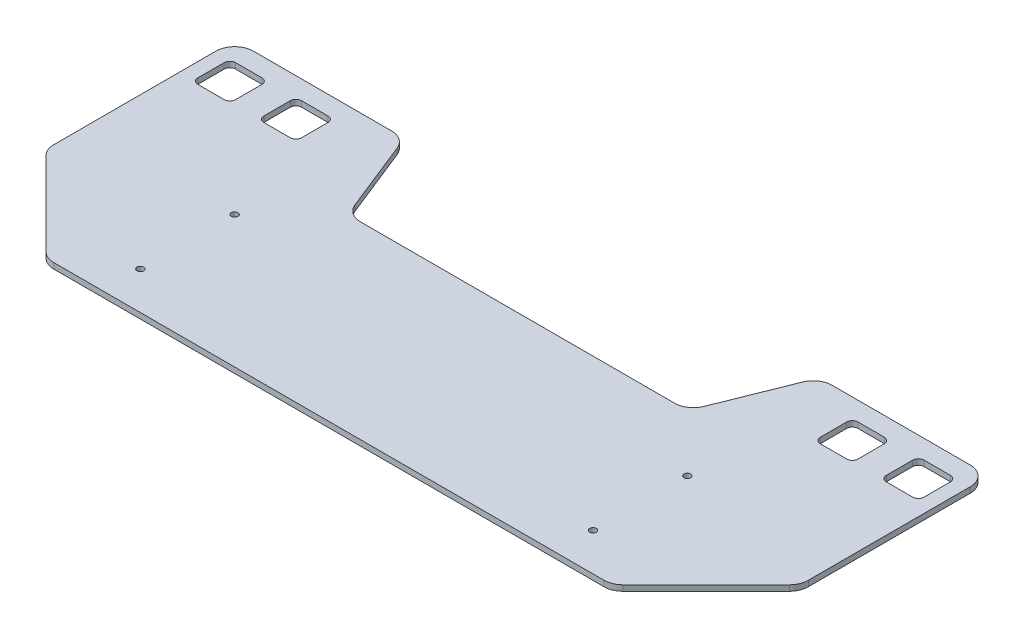
SolidWorks part; units mm, degrees
ref_plane "前视基准面" through (0, 0, 0) normal (0, 0, 1) x (1, 0, 0)
ref_plane "上视基准面" through (0, 0, 0) normal (0, 1, 0) x (1, 0, 0)
ref_plane "右视基准面" through (0, 0, 0) normal (1, 0, 0) x (0, 0, -1)
other "Configuration Table"
sketch "草图1" plane through (0, 0, 0) normal (0, 1, 0) x (1, 0, 0)
  line L0 (-197.0711, -27.9289) -> (-152.9289, -72.0711)
  line L1 (-145.8579, -75) -> (145.8579, -75)
  line L2 (-200, -20.8579) -> (-200, 65)
  line L3 (-190, 75) -> (-116.7703, 75)
  line L4 (200, -20.8579) -> (200, 65)
  line L5 (-200, -75) -> (200, 75) construction
  line L6 (-200, 75) -> (200, -75) construction
  line L7 (152.9289, -72.0711) -> (197.0711, -27.9289)
  line L8 (0, 0) -> (0, 50000) construction
  line L9 (-107.4856, 68.7139) -> (-92.5144, 31.2861)
  line L10 (-83.2297, 25) -> (83.2297, 25)
  line L11 (107.4856, 68.7139) -> (92.5144, 31.2861)
  line L12 (116.7703, 75) -> (190, 75)
  arc A0 (107.4856, 68.7139) -> (116.7703, 75) centre (116.7703, 65) cw
  arc A1 (92.5144, 31.2861) -> (83.2297, 25) centre (83.2297, 35) cw
  arc A2 (-92.5144, 31.2861) -> (-83.2297, 25) centre (-83.2297, 35) ccw
  arc A3 (-107.4856, 68.7139) -> (-116.7703, 75) centre (-116.7703, 65) ccw
  arc A4 (190, 75) -> (200, 65) centre (190, 65) cw
  arc A5 (-200, 65) -> (-190, 75) centre (-190, 65) cw
  arc A6 (197.0711, -27.9289) -> (200, -20.8579) centre (190, -20.8579) ccw
  arc A7 (152.9289, -72.0711) -> (145.8579, -75) centre (145.8579, -65) cw
  arc A8 (-197.0711, -27.9289) -> (-200, -20.8579) centre (-190, -20.8579) cw
  arc A9 (-152.9289, -72.0711) -> (-145.8579, -75) centre (-145.8579, -65) ccw
  point P0 (0, 0)
  point P17 (0, 25)
  point P19 (110, 75)
  point P22 (90, 25)
  point P25 (-90, 25)
  point P28 (-110, 75)
  point P37 (200, -25)
  point P40 (150, -75)
  point P43 (-200, -25)
  point P46 (-150, -75)
  dimension "D8" = 10
  dimension "D9" = 10
  dimension "D1" = 400
  dimension "D2" = 150
  dimension "D3" = 180
  dimension "D4" = 50
  dimension "D5" = 220
extrude "凸台-拉伸1" add sketch "草图1" along normal blind 3
sketch "草图3" plane through (0, 0, 0) normal (0, -1, 0) x (1, 0, 0)
  line L0 (0, 0) -> (0, 50000) construction
  line L1 (-145.8579, 75) -> (145.8579, 75) construction
  circle A0 centre (-120, 55) radius 1.75
  circle A1 centre (-120, 5) radius 1.75
  circle A2 centre (120, 5) radius 1.75
  circle A3 centre (120, 55) radius 1.75
  dimension "D1" = 3.5
  dimension "D2" = 120
  dimension "D3" = 20
  dimension "D4" = 3.5
  dimension "D5" = 50
extrude "切除-拉伸1" cut sketch "草图3" against normal blind 69
sketch "草图4" plane through (0, 3, 0) normal (0, 1, 0) x (1, 0, 0)
  line L0 (-200, 65) -> (-200, -20.8579) construction
  line L1 (-140.5, 45) -> (-154.5, 45)
  line L2 (-137.5, 48) -> (-137.5, 62)
  line L3 (-140.5, 65) -> (-154.5, 65)
  line L4 (-157.5, 48) -> (-157.5, 62)
  line L5 (-175.5, 45) -> (-189.5, 45)
  line L6 (-172.5, 48) -> (-172.5, 62)
  line L7 (-175.5, 65) -> (-189.5, 65)
  line L8 (-192.5, 48) -> (-192.5, 62)
  line L9 (-116.7703, 75) -> (-190, 75) construction
  line L10 (0, 0) -> (0, 50000) construction
  line L11 (192.5, 48) -> (192.5, 62)
  line L12 (175.5, 65) -> (189.5, 65)
  line L13 (172.5, 48) -> (172.5, 62)
  line L14 (175.5, 45) -> (189.5, 45)
  line L15 (157.5, 48) -> (157.5, 62)
  line L16 (140.5, 65) -> (154.5, 65)
  line L17 (137.5, 48) -> (137.5, 62)
  line L18 (140.5, 45) -> (154.5, 45)
  arc A0 (137.5, 48) -> (140.5, 45) centre (140.5, 48) ccw
  arc A1 (140.5, 65) -> (137.5, 62) centre (140.5, 62) ccw
  arc A2 (157.5, 62) -> (154.5, 65) centre (154.5, 62) ccw
  arc A3 (157.5, 48) -> (154.5, 45) centre (154.5, 48) cw
  arc A4 (172.5, 48) -> (175.5, 45) centre (175.5, 48) ccw
  arc A5 (175.5, 65) -> (172.5, 62) centre (175.5, 62) ccw
  arc A6 (192.5, 62) -> (189.5, 65) centre (189.5, 62) ccw
  arc A7 (192.5, 48) -> (189.5, 45) centre (189.5, 48) cw
  arc A8 (-189.5, 45) -> (-192.5, 48) centre (-189.5, 48) cw
  arc A9 (-172.5, 62) -> (-175.5, 65) centre (-175.5, 62) ccw
  arc A10 (-189.5, 65) -> (-192.5, 62) centre (-189.5, 62) ccw
  arc A11 (-175.5, 45) -> (-172.5, 48) centre (-175.5, 48) ccw
  arc A12 (-154.5, 45) -> (-157.5, 48) centre (-154.5, 48) cw
  arc A13 (-137.5, 62) -> (-140.5, 65) centre (-140.5, 62) ccw
  arc A14 (-154.5, 65) -> (-157.5, 62) centre (-154.5, 62) ccw
  arc A15 (-140.5, 45) -> (-137.5, 48) centre (-140.5, 48) ccw
  point P25 (137.5, 45)
  point P28 (137.5, 65)
  point P31 (157.5, 65)
  point P34 (157.5, 45)
  point P37 (172.5, 45)
  point P40 (172.5, 65)
  point P43 (192.5, 65)
  point P46 (192.5, 45)
  point P49 (-192.5, 45)
  point P52 (-172.5, 65)
  point P55 (-192.5, 65)
  point P58 (-172.5, 45)
  point P61 (-157.5, 45)
  point P64 (-137.5, 65)
  point P67 (-157.5, 65)
  point P70 (-137.5, 45)
  dimension "D11" = 3
  dimension "D1" = 20
  dimension "D2" = 20
  dimension "D3" = 15
  dimension "D4" = 7.5
  dimension "D5" = 20
  dimension "D6" = 20
  dimension "D7" = 10
  dimension "D8" = 20
  dimension "D9" = 20
  dimension "D10" = 10
extrude "切除-拉伸2" cut sketch "草图4" against normal blind 69
